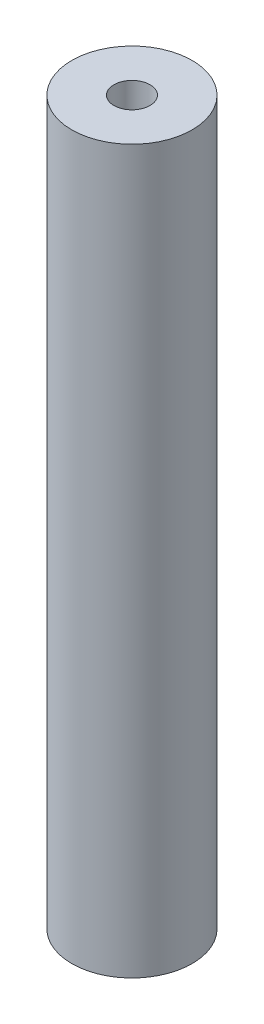
SolidWorks part; units mm, degrees
ref_plane "Front Plane" through (0, 0, 0) normal (0, 0, 1) x (1, 0, 0)
ref_plane "Top Plane" through (0, 0, 0) normal (0, 1, 0) x (1, 0, 0)
ref_plane "Right Plane" through (0, 0, 0) normal (1, 0, 0) x (0, 0, -1)
sketch "Sketch1" plane through (0, 0, 0) normal (0, 1, 0) x (1, 0, 0)
  circle A0 centre (0, 0) radius 5
  circle A1 centre (0, 0) radius 1.5
  dimension "D1" = 10
  dimension "D2" = 3
extrude "Boss-Extrude1" add sketch "Sketch1" along normal blind 60
